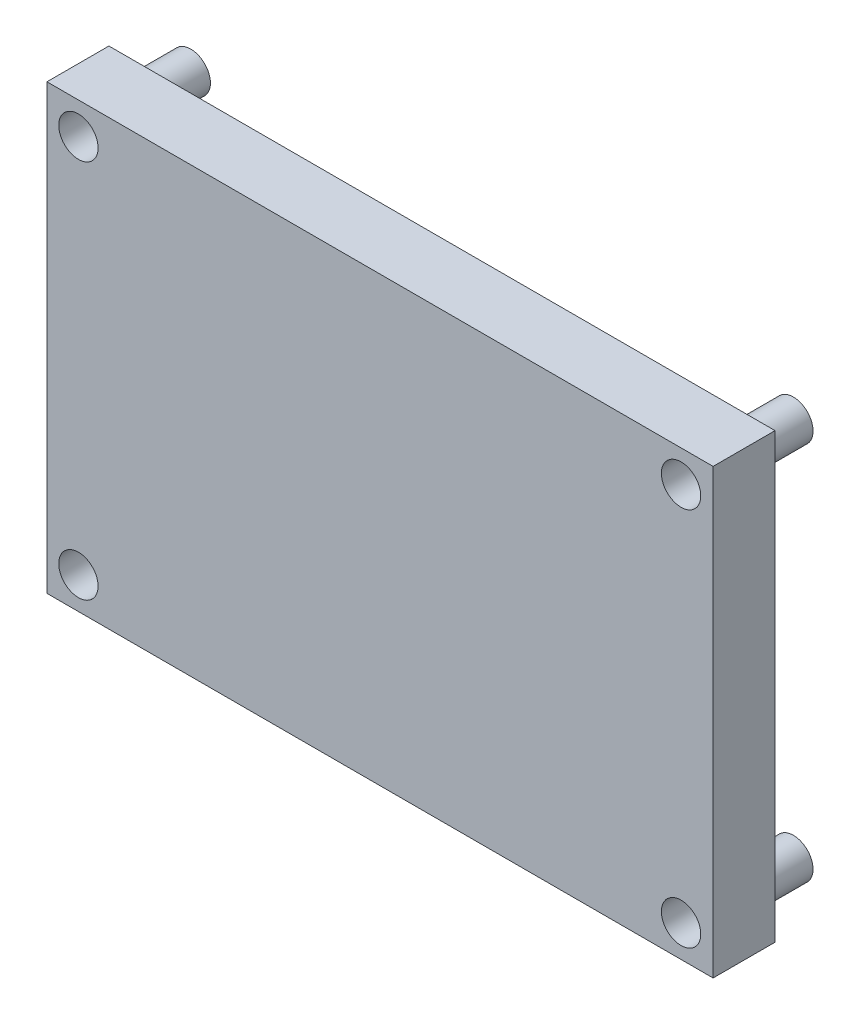
SolidWorks part; units mm, degrees
ref_plane "Front Plane" through (0, 0, 0) normal (0, 0, 1) x (1, 0, 0)
ref_plane "Top Plane" through (0, 0, 0) normal (0, 1, 0) x (1, 0, 0)
ref_plane "Right Plane" through (0, 0, 0) normal (1, 0, 0) x (0, 0, -1)
sketch "Sketch1" plane through (0, 0, 0) normal (0, 0, 1) x (1, 0, 0)
  line L1 (0, 0) -> (86, 0)
  line L2 (0, 0) -> (0, -57.2)
  line L3 (0, -57.2) -> (86, -57.2)
  line L4 (86, 0) -> (86, -57.2)
  circle A0 centre (4.064, -4.1) radius 2.54
  circle A1 centre (81.864, -4.1) radius 2.54
  circle A2 centre (81.864, -53.1) radius 2.54
  circle A3 centre (4.064, -53.1) radius 2.54
  dimension "D3" = 5.08
  dimension "D1" = 86
  dimension "D2" = 57.2
  dimension "D4" = 49
  dimension "D5" = 4.1
  dimension "D6" = 4.064
  dimension "D7" = 77.8
extrude "Boss-Extrude1" add sketch "Sketch1" along normal blind 8
extrude "Boss-Extrude2" add sketch "Sketch1<2>" against normal blind 6.5 separate body contours A0 | A1 | A2 | A3 region at (4.064, -4.1, 0) region at (81.864, -4.1, 0) region at (81.864, -53.1, 0) region at (4.064, -53.1, 0)
sketch "Sketch1<2>" plane through (0, 0, 0) normal (0, 0, 1) x (1, 0, 0) same geometry as "Sketch1"
